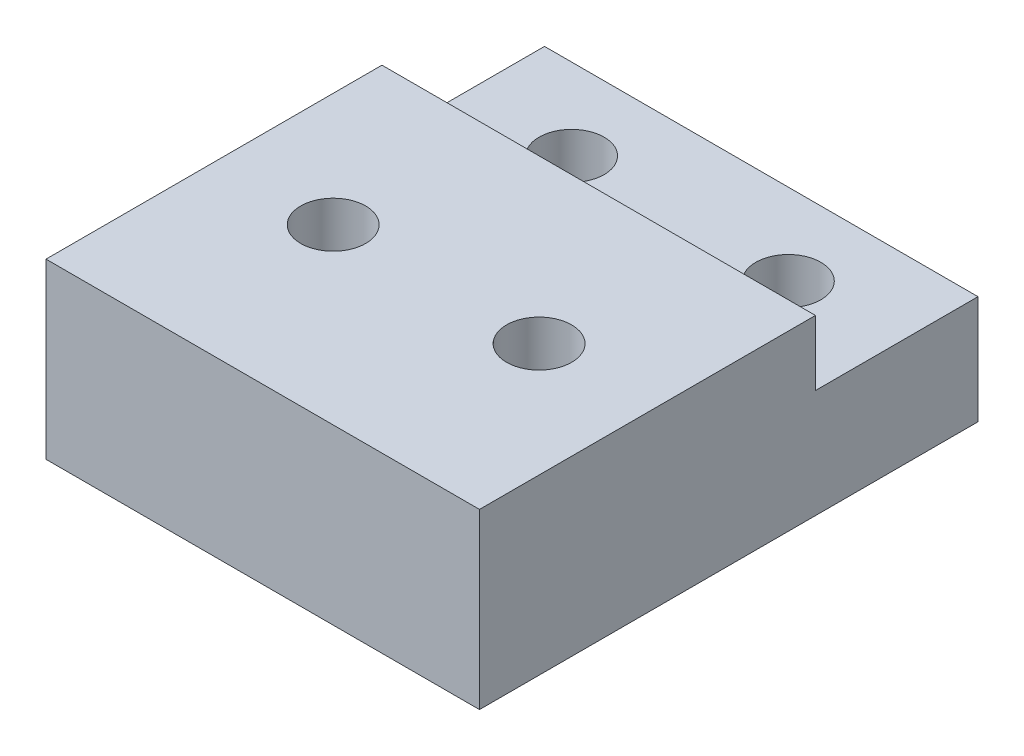
SolidWorks part; units mm, degrees
ref_plane "Front Plane" through (0, 0, 0) normal (0, 0, 1) x (1, 0, 0)
ref_plane "Top Plane" through (0, 0, 0) normal (0, 1, 0) x (1, 0, 0)
ref_plane "Right Plane" through (0, 0, 0) normal (1, 0, 0) x (0, 0, -1)
sketch "Croquis1" plane through (0, 0, 0) normal (0, 1, 0) x (1, 0, 0)
  line L0 (10, -12.5) -> (10, 12.5)
  line L1 (10, -12.5) -> (-10, -12.5)
  line L2 (10, 12.5) -> (-10, 12.5)
  line L3 (-10, -12.5) -> (-10, 12.5)
  line L4 (10, -12.5) -> (-10, 12.5) construction
  line L5 (10, 12.5) -> (-10, -12.5) construction
  line L6 (-10, 5) -> (10, 5)
  point P1 (0, 0)
  dimension "D1" = 20
  dimension "D2" = 17.5
  dimension "D3" = 7.5
extrude "Saliente-Extruir1" add sketch "Croquis1" along normal blind 8 contours L6 L3 L1 L0 region at (0, 0, 3.75)
extrude "Saliente-Extruir2" add sketch "Croquis1<4>" along normal blind 5 contours L3 L6 L0 L2 region at (0, 0, -8.75)
sketch "Croquis1<4>" plane through (0, 0, 0) normal (0, 1, 0) x (1, 0, 0) same geometry as "Croquis1"
sketch "Croquis2" plane through (0, 5, 0) normal (0, 1, 0) x (1, 0, 0)
  line L0 (-10, 5) -> (-10, 12.5) construction
  line L1 (10, 5) -> (10, 12.5) construction
  line L2 (10, 12.5) -> (-10, 12.5) construction
  circle A0 centre (-5, 8.75) radius 1.5
  circle A1 centre (5, 8.75) radius 1.5
  dimension "D1" = 3
  dimension "D2" = 3
  dimension "D3" = 5
  dimension "D4" = 5
  dimension "D5" = 3.75
  dimension "D6" = 3.75
extrude "Cortar-Extruir1" cut sketch "Croquis2" against normal blind 5
sketch "Croquis3" plane through (0, 8, 0) normal (0, 1, 0) x (1, 0, 0)
  line L1 (-10, -12.5) -> (-10, 5) construction
  line L4 (-10, 5) -> (10, 5) construction
  circle A0 centre (-4.75, -2.5) radius 1.5
  circle A1 centre (4.75, -2.5) radius 1.5
  dimension "D1" = 3
  dimension "D2" = 3
  dimension "D3" = 7.5
  dimension "D4" = 7.5
  dimension "D5" = 9.5
  dimension "D6" = 5.25
extrude "Cortar-Extruir2" cut sketch "Croquis3" against normal blind 20
sketch "Croquis4" plane through (0, 8, 0) normal (0, 1, 0) x (1, 0, 0)
  line L0 (10, 5) -> (10, -2.5) construction
  line L1 (10, -12.5) -> (10, 5) construction
  line L2 (10, -2.5) -> (10, -10.5) construction
  line L3 (10, 5) -> (10, -10.5)
  line L4 (10, -10.5) -> (-10, -10.5)
  line L5 (-10, -12.5) -> (-10, 5) construction
  line L6 (-10, -10.5) -> (-10, -12.5)
  line L7 (-10, -12.5) -> (10, -12.5)
  line L8 (10, -12.5) -> (10, -10.5)
  line M6 (-10, 5) -> (-10, -12.5)
  line M7 (-10, -12.5) -> (10, -12.5)
  line M8 (10, -12.5) -> (10, 5)
  dimension "D1" = 8
  dimension "D2" = 7.5
extrude "Cortar-Extruir3" cut sketch "Croquis4" against normal blind 35 contours L4 M8 M6 M7 region at (0, 8, 11.5)
